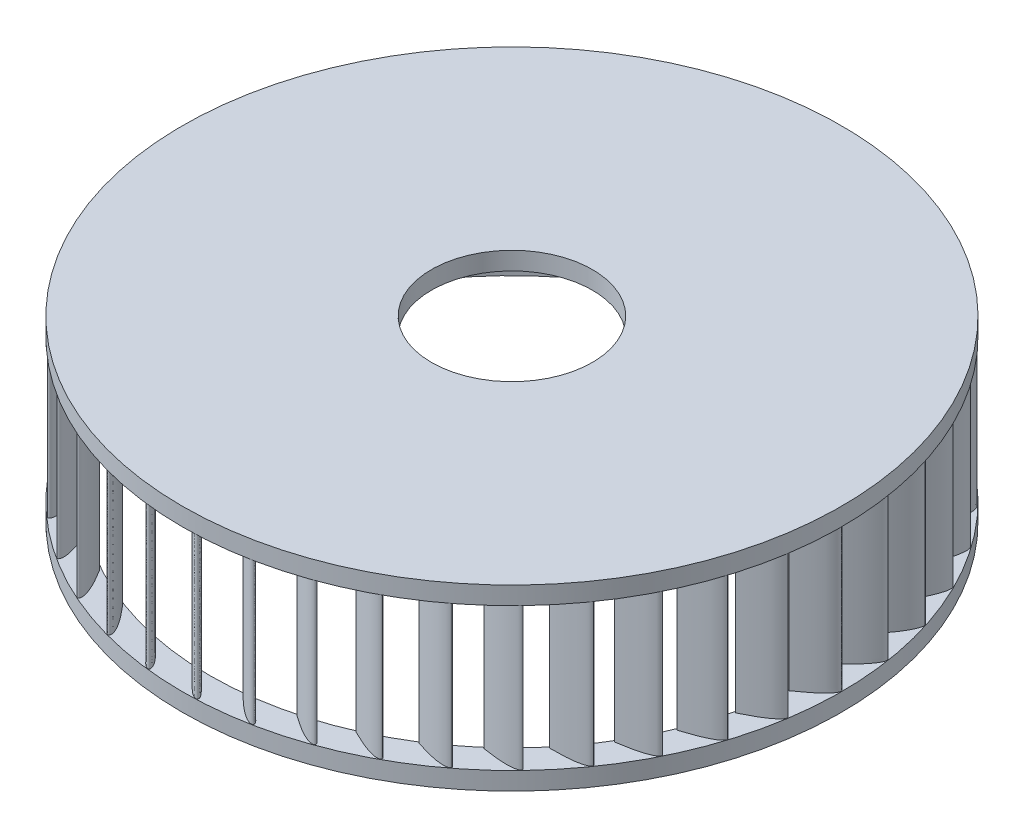
SolidWorks part; units mm, degrees
ref_plane "Alzado" through (0, 0, 0) normal (0, 0, 1) x (1, 0, 0)
ref_plane "Planta" through (0, 0, 0) normal (0, 1, 0) x (1, 0, 0)
ref_plane "Vista lateral" through (0, 0, 0) normal (1, 0, 0) x (0, 0, -1)
sketch "Croquis1" plane through (0, 0, 0) normal (0, 1, 0) x (1, 0, 0)
  line L0 (0, -3375) -> (0, -3685) construction
  circle A0 centre (0, 0) radius 3375
  circle A1 centre (0, 0) radius 3685
  circle A2 centre (0, -3530) radius 12.5
  circle A3 centre (-538.852, -3488.6299) radius 12.5
  circle A4 centre (-1065.0737, -3365.4893) radius 12.5
  circle A5 centre (-1566.331, -3163.4644) radius 12.5
  circle A6 centre (-2030.8749, -2887.2906) radius 12.5
  circle A7 centre (-2447.8167, -2543.4412) radius 12.5
  circle A8 centre (-2807.3838, -2139.9757) radius 12.5
  circle A9 centre (-3101.1482, -1686.351) radius 12.5
  circle A10 centre (-3322.2244, -1193.1996) radius 12.5
  circle A11 centre (-3465.4304, -672.0806) radius 12.5
  circle A12 centre (-3527.4096, -135.2086) radius 12.5
  circle A13 centre (-3506.7094, 404.8325) radius 12.5
  circle A14 centre (-3403.8148, 935.3847) radius 12.5
  circle A15 centre (-3221.1378, 1444.0123) radius 12.5
  circle A16 centre (-2962.96, 1918.7935) radius 12.5
  circle A17 centre (-2635.3329, 2348.5997) radius 12.5
  circle A18 centre (-2245.9358, 2723.3568) radius 12.5
  circle A19 centre (-1803.8959, 3034.2807) radius 12.5
  circle A20 centre (-1319.5743, 3274.0837) radius 12.5
  circle A21 centre (-804.3229, 3437.1448) radius 12.5
  circle A22 centre (-270.2189, 3519.6423) radius 12.5
  circle A23 centre (270.2189, 3519.6423) radius 12.5
  circle A24 centre (804.3229, 3437.1448) radius 12.5
  circle A25 centre (1319.5743, 3274.0837) radius 12.5
  circle A26 centre (1803.8959, 3034.2807) radius 12.5
  circle A27 centre (2245.9358, 2723.3568) radius 12.5
  circle A28 centre (2635.3329, 2348.5997) radius 12.5
  circle A29 centre (2962.96, 1918.7935) radius 12.5
  circle A30 centre (3221.1378, 1444.0123) radius 12.5
  circle A31 centre (3403.8148, 935.3847) radius 12.5
  circle A32 centre (3506.7094, 404.8325) radius 12.5
  circle A33 centre (3527.4096, -135.2086) radius 12.5
  circle A34 centre (3465.4304, -672.0806) radius 12.5
  circle A35 centre (3322.2244, -1193.1996) radius 12.5
  circle A36 centre (3101.1482, -1686.351) radius 12.5
  circle A37 centre (2807.3838, -2139.9757) radius 12.5
  circle A38 centre (2447.8167, -2543.4412) radius 12.5
  circle A39 centre (2030.8749, -2887.2906) radius 12.5
  circle A40 centre (1566.331, -3163.4644) radius 12.5
  circle A41 centre (1065.0737, -3365.4893) radius 12.5
  circle A42 centre (538.852, -3488.6299) radius 12.5
  dimension "D1" = 6750
  dimension "D2" = 7370
  dimension "D3" = 25
  dimension "D4" = 41
extrude "Saliente-Extruir1" add sketch "Croquis1" along normal blind 200 contours A1 | A0
ref_plane "Plano2" through (0, 200, 0) normal (0, 1, 0) x (1, 0, 0)
curve "Curva1"
  spline degree 3 poles (1, 0.0018, 0) (0.9976, 0.0023, 0) (0.9909, 0.0036, 0) (0.9787, 0.006, 0) (0.9627, 0.0091, 0) (0.9439, 0.0126, 0) (0.9229, 0.0164, 0) (0.9003, 0.0205, 0) (0.8762, 0.0247, 0) (0.8509, 0.0289, 0) (0.8246, 0.0333, 0) (0.7975, 0.0376, 0) (0.7697, 0.0418, 0) (0.7414, 0.0461, 0) (0.7127, 0.0502, 0) (0.6836, 0.0542, 0) (0.6543, 0.058, 0) (0.6249, 0.0617, 0) (0.5955, 0.0652, 0) (0.5661, 0.0685, 0) (0.5369, 0.0715, 0) (0.5078, 0.0743, 0) (0.4791, 0.0768, 0) (0.4506, 0.0791, 0) (0.4226, 0.081, 0) (0.3951, 0.0825, 0) (0.368, 0.0837, 0) (0.3416, 0.0846, 0) (0.3157, 0.085, 0) (0.2906, 0.0851, 0) (0.2662, 0.0847, 0) (0.2426, 0.084, 0) (0.2198, 0.0828, 0) (0.1979, 0.0812, 0) (0.1769, 0.0792, 0) (0.1569, 0.0768, 0) (0.1379, 0.074, 0) (0.12, 0.0708, 0) (0.1031, 0.0672, 0) (0.0874, 0.0632, 0) (0.0729, 0.0589, 0) (0.0595, 0.0543, 0) (0.0474, 0.0494, 0) (0.0366, 0.0442, 0) (0.0271, 0.0386, 0) (0.019, 0.0329, 0) (0.0122, 0.0268, 0) (0.0068, 0.0205, 0) (0.0029, 0.0139, 0) (0.0005, 0.007, 0) (-0.0003, 0, 0) (0.0005, -0.007, 0) (0.0029, -0.0139, 0) (0.0068, -0.0205, 0) (0.0122, -0.0268, 0) (0.019, -0.0329, 0) (0.0271, -0.0386, 0) (0.0366, -0.0442, 0) (0.0474, -0.0494, 0) (0.0595, -0.0543, 0) (0.0729, -0.0589, 0) (0.0874, -0.0632, 0) (0.1031, -0.0672, 0) (0.12, -0.0708, 0) (0.1379, -0.074, 0) (0.1569, -0.0768, 0) (0.1769, -0.0792, 0) (0.1979, -0.0812, 0) (0.2198, -0.0828, 0) (0.2426, -0.084, 0) (0.2662, -0.0847, 0) (0.2906, -0.0851, 0) (0.3157, -0.085, 0) (0.3416, -0.0846, 0) (0.368, -0.0837, 0) (0.3951, -0.0825, 0) (0.4226, -0.081, 0) (0.4506, -0.0791, 0) (0.4791, -0.0768, 0) (0.5078, -0.0743, 0) (0.5369, -0.0715, 0) (0.5661, -0.0685, 0) (0.5955, -0.0652, 0) (0.6249, -0.0617, 0) (0.6543, -0.058, 0) (0.6836, -0.0542, 0) (0.7127, -0.0502, 0) (0.7414, -0.0461, 0) (0.7697, -0.0418, 0) (0.7975, -0.0376, 0) (0.8246, -0.0333, 0) (0.8509, -0.0289, 0) (0.8762, -0.0247, 0) (0.9003, -0.0205, 0) (0.9229, -0.0164, 0) (0.9439, -0.0126, 0) (0.9627, -0.0091, 0) (0.9787, -0.006, 0) (0.9909, -0.0036, 0) (0.9976, -0.0023, 0) (1, -0.0018, 0) knots 0 0 0 0 0.003547 0.009905 0.017961 0.027291 0.037633 0.048802 0.060657 0.073083 0.085982 0.099273 0.112881 0.126742 0.140797 0.154992 0.169279 0.18361 0.197944 0.212241 0.226462 0.240572 0.254538 0.268329 0.281913 0.295263 0.308351 0.321153 0.333643 0.3458 0.357602 0.369027 0.380059 0.390677 0.400866 0.41061 0.419894 0.428705 0.437031 0.444862 0.452189 0.459007 0.465313 0.471109 0.476404 0.481216 0.485577 0.489541 0.493185 0.496623 0.5 0.503377 0.506815 0.510459 0.514423 0.518784 0.523596 0.528891 0.534687 0.540993 0.547811 0.555138 0.562969 0.571295 0.580106 0.58939 0.599134 0.609323 0.619941 0.630973 0.642398 0.6542 0.666357 0.678847 0.691649 0.704737 0.718087 0.731671 0.745462 0.759428 0.773538 0.787759 0.802056 0.81639 0.830721 0.845008 0.859203 0.873258 0.887119 0.900727 0.914018 0.926917 0.939343 0.951198 0.962367 0.972709 0.982039 0.990095 0.996453 1 1 1 1
sketch "Croquis3" plane through (0, 200, 0) normal (0, 1, 0) x (1, 0, 0)
  line L0 (0, -3375) -> (0, -3685)
  circle A2 centre (0, 0) radius 3375 construction
  circle A3 centre (0, 0) radius 3685 construction
  point P7 (0, -3530)
sketch "Croquis2" plane through (0, 200, 0) normal (0, 1, 0) x (1, 0, 0)
  line L0 (-155.5508, -3389.0434) -> (-154.4942, -3387.8862)
  line L1 (155.0225, -3671.5352) -> (-155.0225, -3388.4648) construction
  spline S0 degree 3 poles (-155.5508, -3389.0434) (-153.4263, -3391.929) (-150.4647, -3395.9282) (-145.7735, -3402.2079) (-141.9789, -3407.2514) (-137.765, -3412.8093) (-133.5646, -3418.3154) (-128.7556, -3424.575) (-123.0334, -3431.9613) (-116.8681, -3439.8471) (-110.9278, -3447.3723) (-105.7294, -3453.9038) (-100.3765, -3460.5861) (-94.1322, -3468.3202) (-87.2751, -3476.7267) (-80.3468, -3485.1386) (-74.0907, -3492.6632) (-67.9042, -3500.0345) (-62.586, -3506.3167) (-57.5198, -3512.2527) (-52.8337, -3517.7027) (-47.9759, -3523.3083) (-42.7236, -3529.3184) (-37.0785, -3535.7141) (-31.6188, -3541.8315) (-26.1793, -3547.8644) (-20.8302, -3553.7336) (-15.2193, -3559.8126) (-9.432, -3566.004) (-3.9716, -3571.7634) (1.2673, -3577.2102) (5.7522, -3581.8147) (10.6566, -3586.7866) (15.8646, -3591.987) (21.5273, -3597.5384) (27.2217, -3603.0164) (33.507, -3608.9374) (39.4634, -3614.4039) (45.3522, -3619.6738) (50.4779, -3624.1548) (56.508, -3629.2879) (62.3223, -3634.0815) (68.2278, -3638.7767) (73.4934, -3642.8284) (79.9743, -3647.6354) (86.7976, -3652.4299) (93.4078, -3656.7687) (98.6743, -3660.0339) (103.6664, -3662.9596) (108.8415, -3665.7837) (114.018, -3668.371) (118.9122, -3670.5793) (123.6364, -3672.4616) (128.1408, -3673.9905) (132.0722, -3675.062) (135.3863, -3675.7479) (138.2918, -3676.1745) (141.0165, -3676.3754) (143.7, -3676.3481) (146.1421, -3676.0931) (148.5485, -3675.5487) (150.5705, -3674.7918) (152.8288, -3673.5712) (154.7857, -3671.9447) (156.3896, -3669.8613) (157.4306, -3667.9309) (158.101, -3666.0299) (158.5888, -3663.7965) (158.8188, -3661.2551) (158.706, -3658.2984) (158.198, -3654.632) (157.3312, -3651.1408) (156.267, -3647.8891) (155.3895, -3645.536) (154.442, -3643.2342) (153.4229, -3640.9619) (152.3744, -3638.7877) (151.3888, -3636.856) (150.3915, -3634.9874) (149.3998, -3633.2059) (148.3117, -3631.3232) (147.2415, -3629.5363) (146.0784, -3627.6571) (144.9295, -3625.8557) (143.7296, -3624.0282) (142.6194, -3622.3808) (141.5007, -3620.7566) (140.3996, -3619.1906) (139.1726, -3617.4812) (138.017, -3615.9042) (136.8128, -3614.2899) (135.6548, -3612.7632) (134.4137, -3611.1555) (133.2008, -3609.6093) (132.0337, -3608.1441) (130.9019, -3606.7427) (129.6718, -3605.2385) (128.4364, -3603.7495) (127.2176, -3602.2999) (126.1418, -3601.0341) (125.0396, -3599.7505) (123.7007, -3598.2075) (122.2151, -3596.5183) (120.4541, -3594.5443) (118.4141, -3592.2904) (115.8875, -3589.5485) (113.0501, -3586.5314) (110.2257, -3583.5879) (107.6614, -3580.9621) (105.1571, -3578.4346) (102.4861, -3575.7769) (99.5791, -3572.9301) (96.4014, -3569.8659) (93.3453, -3566.9657) (90.2693, -3564.0886) (87.4173, -3561.4543) (84.5767, -3558.8626) (81.5223, -3556.107) (78.5263, -3553.437) (75.1318, -3550.4468) (71.7996, -3547.5455) (67.9241, -3544.2121) (64.1019, -3540.9654) (59.8716, -3537.4161) (56.0781, -3534.2719) (52.4154, -3531.2681) (49.1381, -3528.6029) (45.8606, -3525.9604) (42.5927, -3523.3466) (39.3856, -3520.8003) (35.9666, -3518.1062) (31.9926, -3514.9989) (27.8395, -3511.7813) (23.7174, -3508.6162) (19.9628, -3505.7539) (16.1832, -3502.8924) (12.1906, -3499.8909) (8.0899, -3496.8299) (3.8715, -3493.7033) (-0.3358, -3490.6064) (-5.1086, -3487.1166) (-9.5108, -3483.9224) (-14.7205, -3480.1668) (-19.648, -3476.6391) (-25.8562, -3472.2296) (-32.2421, -3467.7301) (-38.7692, -3463.1722) (-44.3105, -3459.3324) (-48.8189, -3456.2259) (-52.9714, -3453.3784) (-57.072, -3450.5802) (-61.6961, -3447.44) (-66.4574, -3444.2241) (-71.4966, -3440.8405) (-76.3802, -3437.5788) (-80.7072, -3434.7048) (-84.8307, -3431.9787) (-88.494, -3429.5668) (-92.2056, -3427.1341) (-95.7556, -3424.8165) (-99.295, -3422.5151) (-102.8802, -3420.1938) (-106.8854, -3417.6113) (-111.0361, -3414.9479) (-115.3611, -3412.1873) (-119.3293, -3409.6669) (-122.8462, -3407.4437) (-126.2001, -3405.3322) (-129.4035, -3403.3235) (-132.8681, -3401.1605) (-136.1119, -3399.1446) (-139.3225, -3397.1576) (-142.2592, -3395.3476) (-145.0262, -3393.6492) (-149.048, -3391.1888) (-152.148, -3389.3044) (-154.4942, -3387.8862) knots 0 0 0 0 0.012374 0.017185 0.027069 0.03417 0.041272 0.050985 0.06143 0.073539 0.085553 0.094538 0.102366 0.11512 0.128865 0.13983 0.152755 0.162658 0.173063 0.181179 0.189608 0.197885 0.206795 0.217172 0.227344 0.235111 0.245224 0.254767 0.263679 0.274491 0.282175 0.289777 0.296688 0.306292 0.315193 0.324073 0.333578 0.345013 0.351991 0.360869 0.368523 0.379338 0.38689 0.394576 0.402281 0.414754 0.423369 0.429584 0.436151 0.443349 0.449939 0.456132 0.461886 0.467494 0.47255 0.475947 0.479175 0.482686 0.485369 0.488434 0.491146 0.493869 0.49586 0.499995 0.502532 0.504903 0.507539 0.509464 0.512787 0.516319 0.51966 0.525555 0.528709 0.531473 0.534226 0.537304 0.540072 0.54256 0.544792 0.547386 0.549601 0.552302 0.554579 0.557233 0.55968 0.562129 0.564093 0.566491 0.568739 0.571359 0.573242 0.575695 0.577976 0.580256 0.582481 0.584445 0.586477 0.589191 0.591127 0.593017 0.594928 0.596969 0.600072 0.602697 0.606105 0.61057 0.615572 0.620408 0.624657 0.628247 0.632695 0.637669 0.642298 0.647939 0.652218 0.656843 0.661347 0.665498 0.671049 0.675205 0.68112 0.686307 0.692858 0.698438 0.705376 0.709874 0.714796 0.719964 0.724412 0.729247 0.734106 0.739445 0.746668 0.752249 0.757392 0.762972 0.76862 0.774642 0.780644 0.786753 0.792683 0.801062 0.805535 0.814861 0.82199 0.831832 0.841839 0.849482 0.855114 0.860746 0.86687 0.872257 0.880049 0.886712 0.893218 0.900329 0.904651 0.910289 0.915475 0.919976 0.92493 0.930055 0.934725 0.941388 0.947086 0.952445 0.957622 0.961454 0.966131 0.970679 0.975559 0.97932 0.983718 0.987472 0.990532 1 1 1 1
extrude "Saliente-Extruir2" add sketch "Croquis2" along normal blind 1596
sketch "Croquis4" plane through (0, 0, 0) normal (0, 0, 1) x (1, 0, 0)
  line L0 (0, 0) -> (0, 1546.4135)
pattern_circular "MatrizC1" count 41 over 360 about axis through (0, 0, 0) along (0, 1, 0) of "Saliente-Extruir2" reverse direction yes
ref_plane "Plano1" through (0, 1796, 0) normal (0, 1, 0) x (1, 0, 0)
sketch "Croquis5" plane through (0, 1796, 0) normal (0, 1, 0) x (1, 0, 0)
  circle A0 centre (0, 0) radius 900
  circle A1 centre (0, 0) radius 3685
  circle A2 centre (0, 0) radius 3685 construction
  dimension "D1" = 1800
extrude "Saliente-Extruir3" add sketch "Croquis5" along normal blind 200
sketch "Croquis6" plane through (0, 0, 0) normal (1, 0, 0) x (0, 0, -1)
  line L0 (0, 0) -> (0, 1996) construction
  line L1 (3685, 1996) -> (-3685, 1996) construction
  point P5 (0, 998)
ref_plane "Plano medio" through (0, 998, 0) normal (0, 1, 0) x (1, 0, 0)
